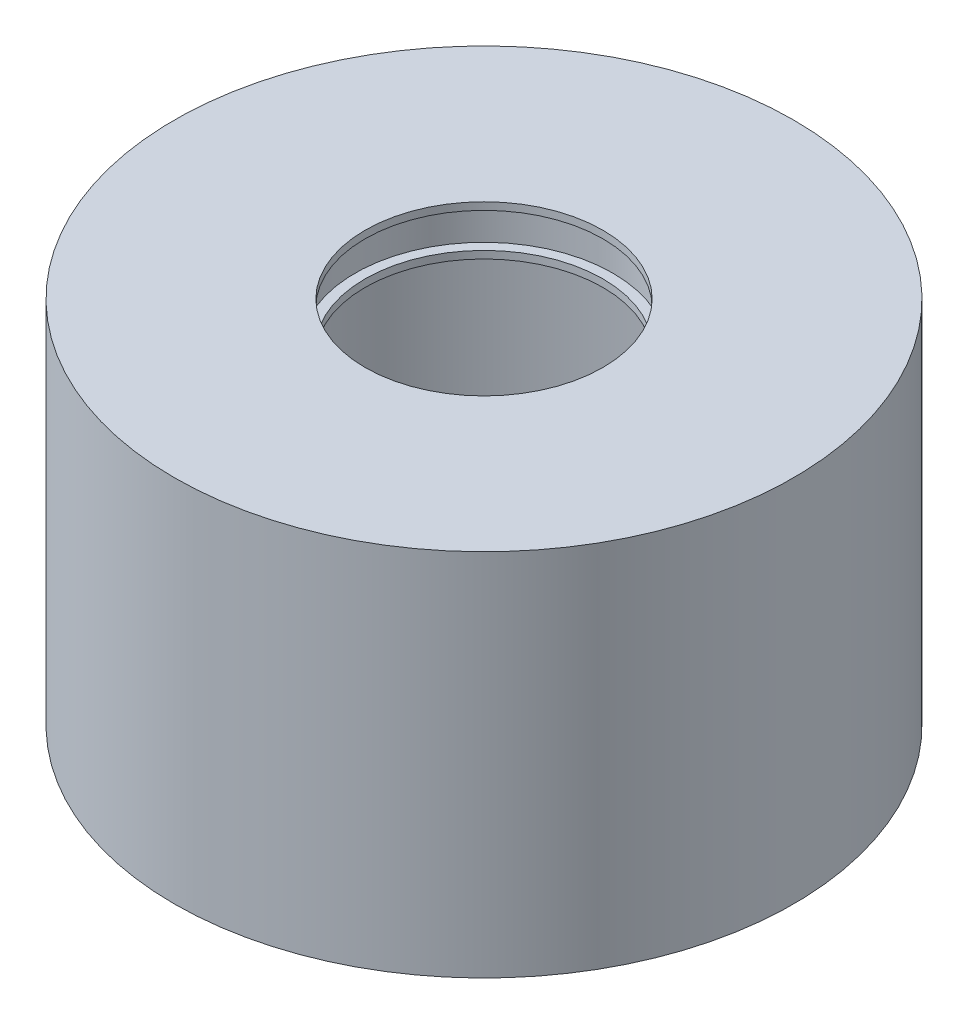
SolidWorks part; units mm, degrees
ref_plane "Front Plane" through (0, 0, 0) normal (0, 0, 1) x (1, 0, 0)
ref_plane "Top Plane" through (0, 0, 0) normal (0, 1, 0) x (1, 0, 0)
ref_plane "Right Plane" through (0, 0, 0) normal (1, 0, 0) x (0, 0, -1)
sketch "Sketch2" plane through (0, 0, 0) normal (1, 0, 0) x (0, 0, -1)
  line L0 (47.5, -37.25) -> (62.5, -37.25)
  line L1 (62.5, -37.25) -> (62.5, 37.25)
  line L2 (62.5, 37.25) -> (24, 37.25)
  line L3 (24, 37.25) -> (24, 35.75)
  line L4 (24, 35.75) -> (26, 35.75)
  line L5 (26, 35.75) -> (26, 28.75)
  line L6 (26, 28.75) -> (24, 28.75)
  line L7 (24, 28.75) -> (24, 27.25)
  line L8 (24, 27.25) -> (47.5, 27.25)
  line L9 (47.5, 27.25) -> (53, 21.75)
  line L11 (47.5, -25.75) -> (50, -25.75)
  line L12 (50, -25.75) -> (50, -35.75)
  line L13 (50, -35.75) -> (47.5, -35.75)
  line L14 (47.5, -35.75) -> (47.5, -37.25)
  line L15 (47.5, -25.75) -> (47.5, -24.25)
  line L16 (47.5, -24.25) -> (53, -18.75)
  line L17 (53, -18.75) -> (53, 21.75)
  line L18 (0, -15.4373) -> (0, -9.583) construction
  line L19 (0, 0) -> (62.5, 0) construction
  point P23 (5.0911, 3.7536)
  point P24 (4.749, 13.4781)
  point P25 (2.5744, 14.6998)
  point P26 (-15.0976, 17.7874)
  point P27 (-3.3366, 11.8127)
  point P28 (5.8694, -19.5135)
  point P29 (52.5, 19.2305)
  dimension "D1" = 10
  dimension "D2" = 7
  dimension "D3" = 1.5
  dimension "D4" = 100
  dimension "D5" = 52
  dimension "D6" = 71.5
  dimension "D7" = 125
  dimension "D8" = 2
  dimension "D9" = 2.5
  dimension "D10" = 106
  dimension "D11" = 45
revolve "Revolve1" add sketch "Sketch2" angle 360 about L18
sketch "Sketch3" plane through (0, -25.75, 0) normal (0, -1, 0) x (1, 0, 0)
  line L0 (-47.2909, 16.235) -> (0, 0) construction
  line L1 (0, 0) -> (-50, 0) construction
  circle A0 centre (0, 0) radius 50 construction
  circle A1 centre (-47.2909, 16.235) radius 2
  circle A2 centre (-39.9594, 30.0541) radius 2
  circle A3 centre (-28.7164, 40.9312) radius 2
  circle A4 centre (-14.6625, 47.8018) radius 2
  circle A5 centre (0.8267, 49.9932) radius 2
  circle A6 centre (16.235, 47.2909) radius 2
  circle A7 centre (30.0541, 39.9594) radius 2
  circle A8 centre (40.9312, 28.7164) radius 2
  circle A9 centre (47.8018, 14.6625) radius 2
  circle A10 centre (49.9932, -0.8267) radius 2
  circle A11 centre (47.2909, -16.235) radius 2
  circle A12 centre (39.9594, -30.0541) radius 2
  circle A13 centre (28.7164, -40.9312) radius 2
  circle A14 centre (14.6625, -47.8018) radius 2
  circle A15 centre (-0.8267, -49.9932) radius 2
  circle A16 centre (-16.235, -47.2909) radius 2
  circle A17 centre (-30.0541, -39.9594) radius 2
  circle A18 centre (-40.9312, -28.7164) radius 2
  circle A19 centre (-47.8018, -14.6625) radius 2
  circle A20 centre (-49.9932, 0.8267) radius 2
  point P45 (0, 0)
  dimension "D1" = 4
  dimension "D2" = 100
  dimension "D4" = 18.947
  dimension "D3" = 20
extrude "Cut-Extrude5" cut sketch "Sketch3" against normal blind 50 from offset 2.5 offset against normal yes
